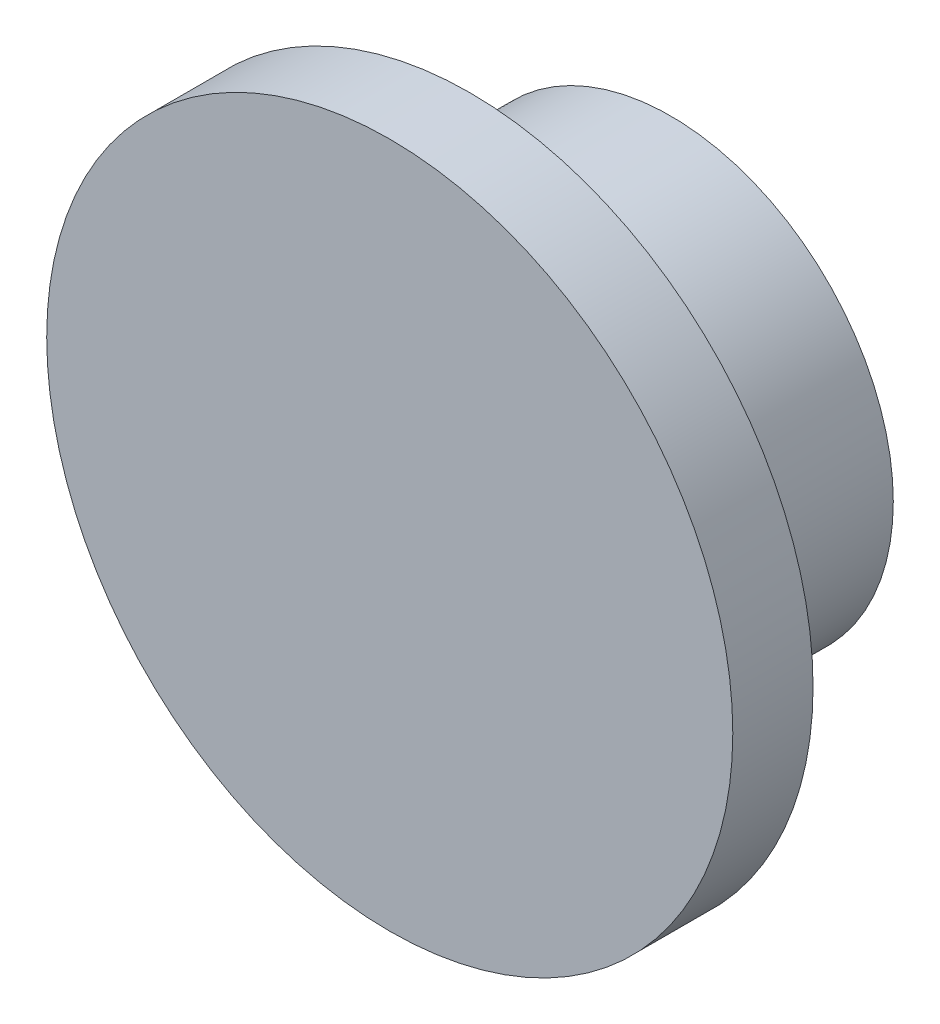
SolidWorks part; units mm, degrees
ref_plane "Front Plane" through (0, 0, 0) normal (0, 0, 1) x (1, 0, 0)
ref_plane "Top Plane" through (0, 0, 0) normal (0, 1, 0) x (1, 0, 0)
ref_plane "Right Plane" through (0, 0, 0) normal (1, 0, 0) x (0, 0, -1)
sketch "Sketch1" plane through (0, 0, 0) normal (0, 0, 1) x (1, 0, 0)
  circle A0 centre (0, 0) radius 2.55
  circle A3 centre (0, 0) radius 2.35 construction
  circle A4 centre (0, 0) radius 5.55
  dimension "D1" = 4.7
  dimension "D2" = 0.2
  dimension "D3" = 3
extrude "Boss-Extrude1" add sketch "Sketch1" against normal blind 5
sketch "Sketch2" plane through (0, 0, 0) normal (0, 0, 1) x (1, 0, 0)
  circle A2 centre (0, 0) radius 8.55
  circle A3 centre (0, 0) radius 8.55
  dimension "D1" = 3
extrude "Boss-Extrude2" add sketch "Sketch2" along normal blind 2
thread "Thread1" pitch 0.8 method extrude profile "Thread Profile1" start angle 0, offset 0, length 4.5, pitch 0.8, diameter 5.1
ref_plane "Plane1" through (2.55, 0, -5) normal (0, -1, 0) x (1, 0, 0)
sketch "Thread Profile1" plane through (2.55, 0, -5) normal (0, -1, 0) x (1, 0, 0)
  line L0 (0, 0) -> (0, 0.8) construction
  line L11 (0, 0) -> (0, 0.7)
  line L12 (0, 0.7) -> (-0.433, 0.45)
  line L13 (-0.433, 0.45) -> (-0.433, 0.25)
  line L15 (-0.433, 0.25) -> (0, 0)
  line L17 (-0.433, 0.35) -> (0, 0.35) construction
  point P2 (0, 0)
  dimension "Pitch" = 0.8
  dimension "Profile_Angle" = 60
  dimension "Profile_Land" = 0.2
  dimension "Profile_Height" = 0.433
sketch "Sketch3" [suppressed] plane through (0, 0, 2) normal (0, 0, 1) x (1, 0, 0)
  line L0 (0, 4.3) -> (0, -4.3) construction
  line L1 (-0.375, -4.3) -> (0.375, -4.3)
  line L2 (-0.375, 4.3) -> (0.375, 4.3)
  line L3 (0.375, -4.3) -> (0.375, 4.3)
  line L4 (-0.375, 4.3) -> (-0.375, -4.3)
  circle A0 centre (0, 0) radius 4.3 construction
  point P7 (0, 0)
  point P11 (0, -4.3)
  point P14 (0, 4.3)
  dimension "D1" = 0.75
extrude "Cut-Extrude1" [suppressed] cut sketch "Sketch3" against normal blind 1
equation "\"ThreadWalls\"= 3"
equation "\"D3@Sketch1\"=\"ThreadWalls\""
equation "\"BaseFlange\"= 3"
equation "\"D1@Sketch2\"=\"BaseFlange\""
